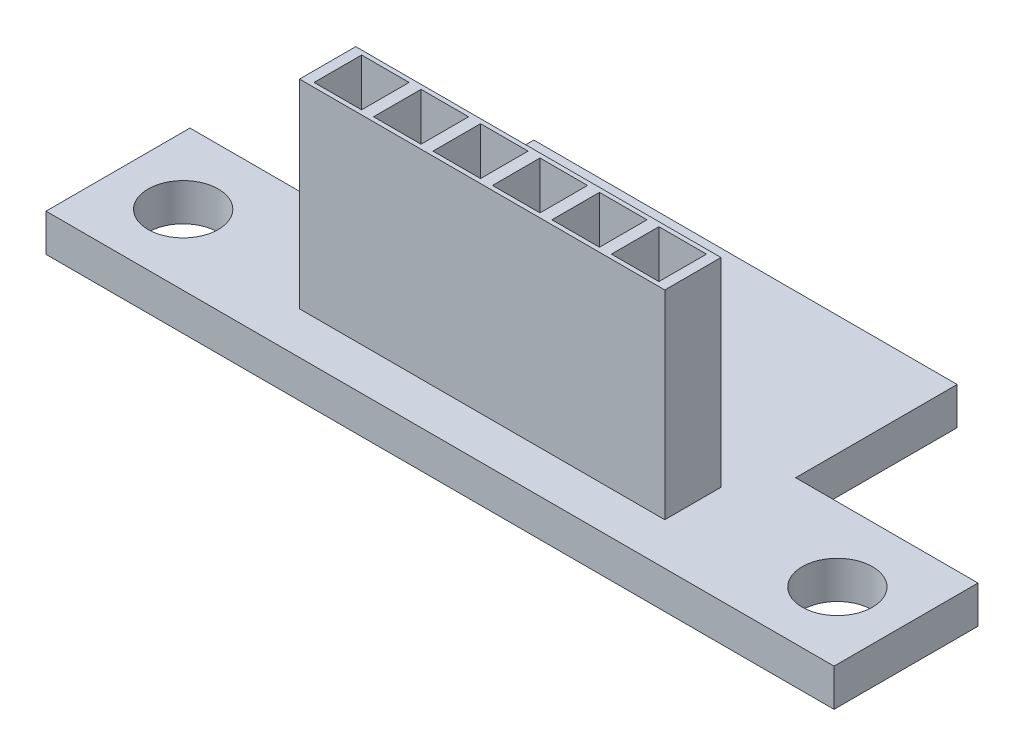
SolidWorks part; units mm, degrees
ref_plane "Front Plane" through (0, 0, 0) normal (0, 0, 1) x (1, 0, 0)
ref_plane "Top Plane" through (0, 0, 0) normal (0, 1, 0) x (1, 0, 0)
ref_plane "Right Plane" through (0, 0, 0) normal (1, 0, 0) x (0, 0, -1)
sketch "Sketch1" plane through (0, 0, 0) normal (0, 1, 0) x (1, 0, 0)
  line L1 (-16.8287, -6.5239) -> (16.8287, -6.5239)
  line L2 (-16.8287, -6.5239) -> (-16.8287, 6.5239)
  line L3 (-16.8287, 6.5239) -> (16.8287, 6.5239)
  line L4 (16.8287, -6.5239) -> (16.8287, 6.5239)
  line L5 (-16.8287, -6.5239) -> (16.8287, 6.5239) construction
  line L6 (-16.8287, 6.5239) -> (16.8287, -6.5239) construction
  point P0 (0, 0)
extrude "Boss-Extrude1" add sketch "Sketch1" along normal blind 1.6
sketch "Sketch2" plane through (0, 1.6, 0) normal (0, 1, 0) x (1, 0, 0)
  line L0 (-13.97, -3.5239) -> (13.97, -3.5239) construction
  line L1 (-7.8, -4.7239) -> (7.8, -4.7239)
  line L2 (-7.8, -4.7239) -> (-7.8, -2.3239)
  line L3 (-7.8, -2.3239) -> (7.8, -2.3239)
  line L4 (7.8, -4.7239) -> (7.8, -2.3239)
  line L5 (-7.8, -4.7239) -> (7.8, -2.3239) construction
  line L6 (-7.8, -2.3239) -> (7.8, -4.7239) construction
  line L7 (-16.8287, -6.5239) -> (16.8287, -6.5239) construction
  circle A0 centre (-13.97, -3.5239) radius 1.5
  circle A1 centre (13.97, -3.5239) radius 1.5
  point P0 (0, -3.5239)
  point P10 (0, -3.5239)
  dimension "D5" = 3
  dimension "D1" = 15.6
  dimension "D2" = 2.4
  dimension "D3" = 27.94
  dimension "D4" = 3
extrude "Boss-Extrude2" add sketch "Sketch2" along normal blind 8.5 separate body contours L1 L4 L3 L2 region at (0, 1.6, 3.5239)
extrude "Cut-Extrude2" cut sketch "Sketch2<3>" against normal through all contours A0 | A1 region at (-13.97, 1.6, 3.5239) region at (13.97, 1.6, 3.5239)
sketch "Sketch2<3>" plane through (0, 1.6, 0) normal (0, 1, 0) x (1, 0, 0) same geometry as "Sketch2"
sketch "Sketch3" plane through (0, 10.1, 0) normal (0, 1, 0) x (1, 0, 0)
  line L0 (-6.35, -3.5239) -> (6.35, -3.5239) construction
  line L5 (7.8, -4.7239) -> (7.8, -2.3239) construction
  line L6 (-2.7949, -4.539) -> (-2.7949, -2.5088)
  line L7 (-7.3651, -4.539) -> (-5.3349, -4.539)
  line L8 (-7.3651, -4.539) -> (-7.3651, -2.5088)
  line L9 (-7.3651, -2.5088) -> (-5.3349, -2.5088)
  line L10 (-5.3349, -4.539) -> (-5.3349, -2.5088)
  line L11 (-7.3651, -4.539) -> (-5.3349, -2.5088) construction
  line L12 (-7.3651, -2.5088) -> (-5.3349, -4.539) construction
  line L13 (-4.8251, -2.5088) -> (-2.7949, -2.5088)
  line L14 (-4.8251, -4.539) -> (-4.8251, -2.5088)
  line L15 (-4.8251, -4.539) -> (-2.7949, -4.539)
  line L16 (-0.2549, -4.539) -> (-0.2549, -2.5088)
  line L17 (-2.2851, -2.5088) -> (-0.2549, -2.5088)
  line L18 (-2.2851, -4.539) -> (-2.2851, -2.5088)
  line L19 (-2.2851, -4.539) -> (-0.2549, -4.539)
  line L20 (2.2851, -4.539) -> (2.2851, -2.5088)
  line L21 (0.2549, -2.5088) -> (2.2851, -2.5088)
  line L22 (0.2549, -4.539) -> (0.2549, -2.5088)
  line L23 (0.2549, -4.539) -> (2.2851, -4.539)
  line L24 (4.8251, -4.539) -> (4.8251, -2.5088)
  line L25 (2.7949, -2.5088) -> (4.8251, -2.5088)
  line L26 (2.7949, -4.539) -> (2.7949, -2.5088)
  line L27 (2.7949, -4.539) -> (4.8251, -4.539)
  line L28 (7.3651, -4.539) -> (7.3651, -2.5088)
  line L29 (5.3349, -2.5088) -> (7.3651, -2.5088)
  line L30 (5.3349, -4.539) -> (5.3349, -2.5088)
  line L31 (5.3349, -4.539) -> (7.3651, -4.539)
  point P6 (0, -3.5239)
  point P9 (7.8, -3.5239)
  dimension "D1" = 12.7
  dimension "D3" = 2.54
  dimension "D2" = 6
extrude "Cut-Extrude1" cut sketch "Sketch3" against normal blind 8
sketch "Sketch4" plane through (0, 1.6, 0) normal (0, 1, 0) x (1, 0, 0)
  line L1 (-16.8287, 6.5239) -> (-9.04, 6.5239)
  line L2 (-16.8287, 6.5239) -> (-16.8287, -0.3754)
  line L3 (-16.8287, -0.3754) -> (-9.04, -0.3754)
  line L4 (-9.04, 6.5239) -> (-9.04, -0.3754)
  line L5 (16.8287, 6.5239) -> (9.04, 6.5239)
  line L6 (16.8287, 6.5239) -> (16.8287, -0.3754)
  line L7 (16.8287, -0.3754) -> (9.04, -0.3754)
  line L8 (9.04, 6.5239) -> (9.04, -0.3754)
extrude "Cut-Extrude3" cut sketch "Sketch4" against normal through all
equation "\"D3@Sketch2\"=1.1in"
equation "\"D1@Sketch3\"=0.1in*5"
